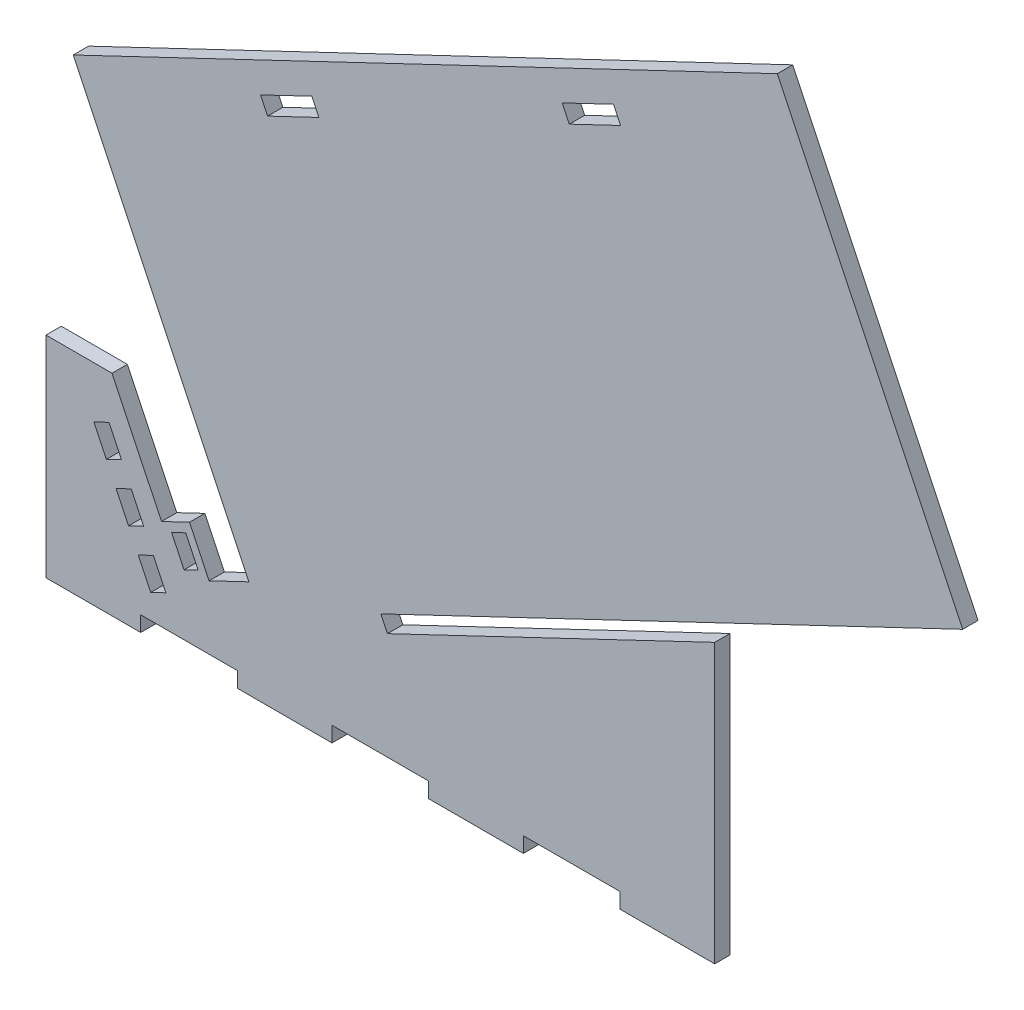
SolidWorks part; units mm, degrees
ref_plane "Front Plane" through (0, 0, 0) normal (0, 0, 1) x (1, 0, 0)
ref_plane "Top Plane" through (0, 0, 0) normal (0, 1, 0) x (1, 0, 0)
ref_plane "Right Plane" through (0, 0, 0) normal (1, 0, 0) x (0, 0, -1)
sketch "Sketch1" plane through (0, 0, 0) normal (0, 0, 1) x (1, 0, 0)
  line L12 (-264.2572, -95.6581) -> (-230.2572, -95.6581)
  line L13 (-230.2572, -95.6581) -> (-230.2572, -90.1581)
  line L15 (-264.2572, -90.1581) -> (-264.2572, -95.6581)
  line L24 (-241.7419, -36.2998) -> (-237.4367, -45.3257)
  line L25 (-237.4367, -45.3257) -> (-242.4912, -47.7366)
  line L26 (-242.4912, -47.7366) -> (-246.7963, -38.7107)
  line L27 (-246.7963, -38.7107) -> (-241.7419, -36.2998)
  line L28 (-233.7774, -52.9977) -> (-229.4723, -62.0235)
  line L29 (-229.4723, -62.0235) -> (-234.5268, -64.4344)
  line L30 (-234.5268, -64.4344) -> (-238.8319, -55.4085)
  line L31 (-238.8319, -55.4085) -> (-233.7774, -52.9977)
  line L32 (-225.8129, -69.6955) -> (-221.5078, -78.7214)
  line L33 (-221.5078, -78.7214) -> (-226.5623, -81.1322)
  line L34 (-226.5623, -81.1322) -> (-230.8674, -72.1064)
  line L35 (-230.8674, -72.1064) -> (-225.8129, -69.6955)
  line L44 (-195.5972, -95.6581) -> (-161.5972, -95.6581)
  line L45 (-195.5972, -90.1581) -> (-195.5972, -95.6581)
  line L47 (-161.5972, -95.6581) -> (-161.5972, -90.1581)
  line L52 (-24.2572, -95.6581) -> (-58.2572, -95.6581)
  line L53 (-58.2572, -95.6581) -> (-58.2572, -90.1581)
  line L55 (-24.2572, -90.1581) -> (-24.2572, -95.6581)
  line L56 (-92.9172, -95.6581) -> (-126.9172, -95.6581)
  line L57 (-126.9172, -95.6581) -> (-126.9172, -90.1581)
  line L59 (-92.9172, -90.1581) -> (-92.9172, -95.6581)
  line L61 (-264.2572, -90.1581) -> (-264.2572, -20.2081)
  line L62 (-264.2572, -20.2081) -> (-240.5538, -20.2081)
  line L63 (-240.5538, -20.2081) -> (-222.803, -57.4233)
  line L64 (-205.7265, -67.3163) -> (-191.4241, -60.4944)
  line L65 (-191.4241, -60.4944) -> (-254.494, 71.7343)
  line L66 (-230.2572, -90.1581) -> (-195.5972, -90.1581)
  line L67 (-161.5972, -90.1581) -> (-126.9172, -90.1581)
  line L68 (-58.2572, -90.1581) -> (-92.9172, -90.1581)
  line L70 (-254.494, 71.7343) -> (-1.7701, 192.2774)
  line L71 (-219.5705, -82.783) -> (-144.0757, -46.7738) construction
  line L80 (-78.6977, 144.5056) -> (-60.646, 153.1158)
  line L81 (-60.646, 153.1158) -> (-58.2782, 148.1516)
  line L82 (-58.2782, 148.1516) -> (-76.3299, 139.5414)
  line L83 (-76.3299, 139.5414) -> (-78.6977, 144.5056)
  line L84 (-187.0079, 92.8442) -> (-168.9562, 101.4545)
  line L85 (-168.9562, 101.4545) -> (-166.5884, 96.4902)
  line L86 (-166.5884, 96.4902) -> (-184.6401, 87.88)
  line L87 (-184.6401, 87.88) -> (-187.0079, 92.8442)
  line L88 (-24.2572, -90.1581) -> (-24.2572, 4.2831)
  line L89 (-144.0757, -46.7738) -> (-141.7079, -51.738)
  line L92 (-141.7079, -51.738) -> (-24.2572, 4.2831)
  line L93 (-144.0757, -46.7738) -> (64.7438, 52.828)
  line L94 (64.7438, 52.828) -> (-1.7701, 192.2774)
  line L106 (-237.1701, -45.4201) -> (-242.5856, -48.0032)
  line L107 (-242.5856, -48.0032) -> (-247.063, -38.6163)
  line L108 (-247.063, -38.6163) -> (-241.6474, -36.0332)
  line L109 (-241.6474, -36.0332) -> (-237.1701, -45.4201)
  line L110 (-229.2057, -62.1179) -> (-234.6212, -64.701)
  line L111 (-234.6212, -64.701) -> (-239.0985, -55.3141)
  line L112 (-239.0985, -55.3141) -> (-233.683, -52.7311)
  line L113 (-233.683, -52.7311) -> (-229.2057, -62.1179)
  line L114 (-231.134, -72.012) -> (-225.7185, -69.4289)
  line L115 (-225.7185, -69.4289) -> (-221.2412, -78.8158)
  line L116 (-221.2412, -78.8158) -> (-226.6567, -81.3988)
  line L117 (-226.6567, -81.3988) -> (-231.134, -72.012)
  line L118 (-166.3218, 96.3958) -> (-184.7345, 87.6134)
  line L119 (-184.7345, 87.6134) -> (-187.2746, 92.9387)
  line L120 (-187.2746, 92.9387) -> (-168.8618, 101.7211)
  line L121 (-168.8618, 101.7211) -> (-166.3218, 96.3958)
  line L122 (-58.0116, 148.0572) -> (-76.4243, 139.2747)
  line L123 (-76.4243, 139.2747) -> (-78.9643, 144.6)
  line L124 (-78.9643, 144.6) -> (-60.5516, 153.3824)
  line L125 (-60.5516, 153.3824) -> (-58.0116, 148.0572)
  line L126 (-222.803, -57.4233) -> (-212.7356, -52.6214)
  line L127 (-212.7356, -52.6214) -> (-205.7265, -67.3163)
  line L128 (-219.2063, -59.0316) -> (-214.1518, -56.6207)
  line L129 (-214.1518, -56.6207) -> (-209.6745, -66.0076)
  line L130 (-209.6745, -66.0076) -> (-214.729, -68.4185)
  line L131 (-214.729, -68.4185) -> (-219.2063, -59.0316)
  dimension "D3" = 8
  dimension "D4" = 8
  dimension "D6" = 10
  dimension "D9" = 10.4
extrude "Boss-Extrude1" add sketch "Sketch1" along normal blind 5.5 contours L93 L94 L70 L65 L64 L63 L62 L61 L15 L12 L13 L66 L45 L44 L47 L67 L57 L56 L59 L68 L53 L52 L55 L88 L92 L89 L120 L121 L118 L119 L112 L113 L110 L111 L108 L109 L106 L107 L116 L117 L114 L115 L124 L125 L122 L123 region at (-102.7738, 32.6302, 0)
